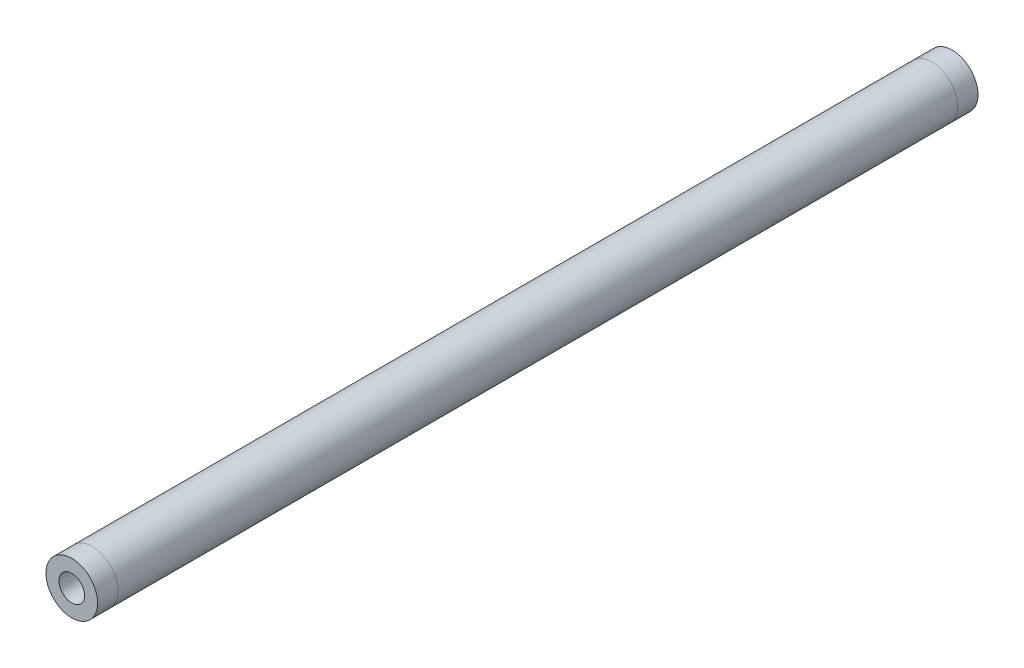
SolidWorks part; units mm, degrees
ref_plane "Front Plane" through (0, 0, 0) normal (0, 0, 1) x (1, 0, 0)
ref_plane "Top Plane" through (0, 0, 0) normal (0, 1, 0) x (1, 0, 0)
ref_plane "Right Plane" through (0, 0, 0) normal (1, 0, 0) x (0, 0, -1)
sketch "Axis" plane through (0, 0, 0) normal (1, 0, 0) x (0, 0, -1)
  line L0 (0, 0) -> (272.762, 0) construction
  line L1 (272.762, 0) -> (266.412, 0)
  line L2 (272.762, 0) -> (301.337, 0) construction
  line L3 (0, 0) -> (-28.575, 0) construction
  point P4 (0, 0)
  point P5 (272.762, 0)
  point P6 (266.412, 0)
  dimension "D1" = 6.35
  dimension "D2" = 28.575
  dimension "D3" = 28.575
sketch "Sketch1" plane through (0, 0, 0) normal (0, 0, 1) x (1, 0, 0)
  circle A0 centre (0, 0) radius 8.001
  circle A1 centre (0, 0) radius 6.477
  circle A2 centre (0, 0) radius 3.9688
  dimension "D1" = 16.002
  dimension "D2" = 1.524
  dimension "D3" = 7.9375
extrude "Threaded insert 1-1" add sketch "Sketch1" against normal blind 6.35 contours A0 A1 | A1 A2 region at (-7.7747, 0, 0) region at (-6.2938, 0, 0)
extrude "Threaded insert 1-2" add sketch "Sketch1<3>" against normal blind 9.525 from surface contours A1 A2 region at (-6.2938, 0, 0) starting at face at (8.001, 0, -6.35)
sketch "Sketch1<3>" plane through (0, 0, 0) normal (0, 0, 1) x (1, 0, 0) same geometry as "Sketch1"
extrude "Tube extrude" add sketch "Sketch1<4>" against normal up to vertex (266.412 mm away) from surface separate body contours A0 A1 region at (-7.7747, 0, 0) up to point (0, 0, -266.412) starting at face at (6.477, 0, -6.35)
sketch "Sketch1<4>" plane through (0, 0, 0) normal (0, 0, 1) x (1, 0, 0) same geometry as "Sketch1"
extrude "Threaded insert 2-1" add sketch "Sketch1<6>" along normal blind 9.525 from surface separate body contours A1 A2 region at (-6.2938, 0, 0) starting at face at (6.477, 0, -266.412)
sketch "Sketch1<6>" plane through (0, 0, 0) normal (0, 0, 1) x (1, 0, 0) same geometry as "Sketch1"
extrude "Threaded insert 2-2" add sketch "Sketch1<9>" against normal blind 6.35 from surface separate body contours A1 A2 | A0 A1 region at (-7.7747, 0, 0) region at (-6.2938, 0, 0) starting at face at (6.477, 0, -266.412)
sketch "Sketch1<9>" plane through (0, 0, 0) normal (0, 0, 1) x (1, 0, 0) same geometry as "Sketch1"
combine bodies "Combine1" operation type add bodies to combine 106 104
equation "\"Threaded insert outer thickness\"= .25"
equation "\"D1@Threaded insert 1-1\"=\"Threaded insert outer thickness\""
equation "\"D1@Threaded insert 2-2\"=\"Threaded insert outer thickness\""
equation "\"D1@Axis\" = \"Threaded insert outer thickness\""
